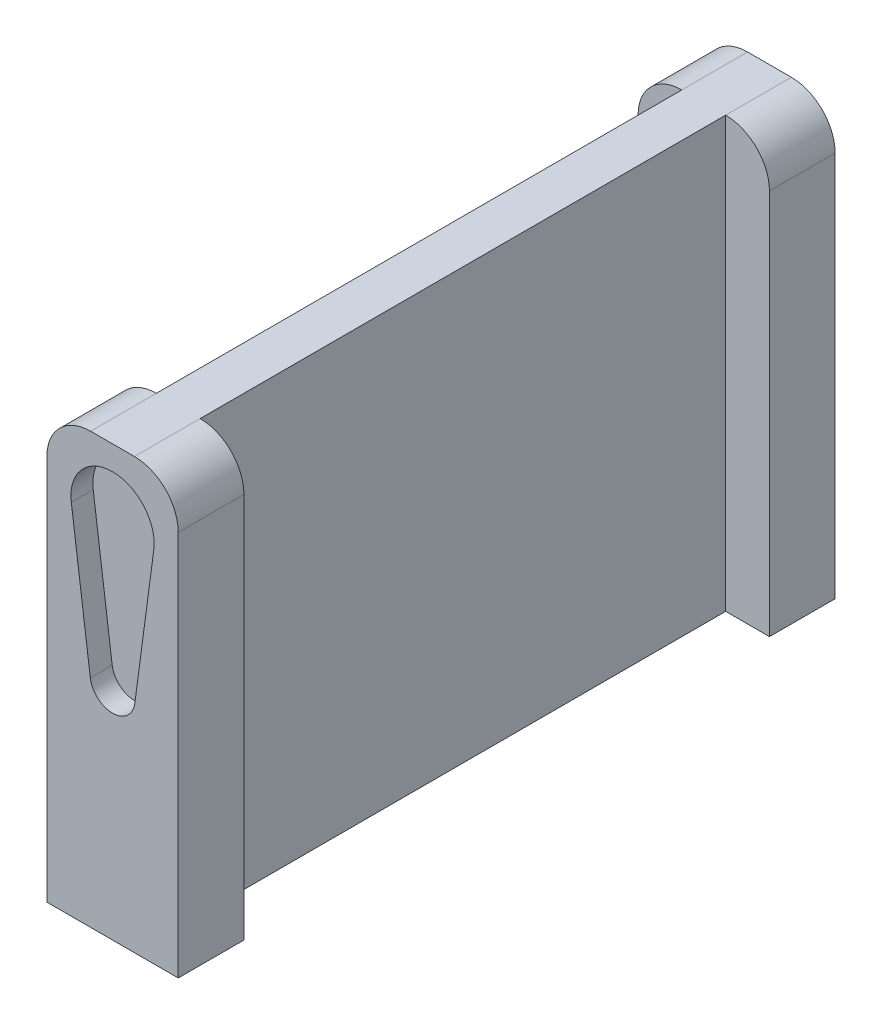
SolidWorks part; units mm, degrees
ref_plane "Front Plane" through (0, 0, 0) normal (0, 0, 1) x (1, 0, 0)
ref_plane "Top Plane" through (0, 0, 0) normal (0, 1, 0) x (1, 0, 0)
ref_plane "Right Plane" through (0, 0, 0) normal (1, 0, 0) x (0, 0, -1)
sketch "Sketch1" plane through (0, 0, 0) normal (0, 0, 1) x (1, 0, 0)
  line L0 (0, 0) -> (0, -13.25) construction
  line L1 (-1.7347, -13.4811) -> (-3.4693, -0.4623) construction
  line L2 (1.7347, -13.4811) -> (3.4693, -0.4623) construction
  circle A0 centre (0, 0) radius 3.5 construction
  circle A1 centre (0, -13.25) radius 1.75 construction
  point P7 (0, -15)
  point P10 (0, 3.5)
  dimension "D1" = 7
  dimension "D3" = 3.5
  dimension "D2" = 18.5
ref_plane "Plane2" through (0, 6, 0) normal (0, 1, 0) x (1, 0, 0)
sketch "Sketch4" plane through (0, 6, 0) normal (0, 1, 0) x (1, 0, 0)
  line L0 (-6, 30) -> (6, 30)
  line L1 (6, 30) -> (6, 24)
  line L2 (6, 24) -> (2, 24)
  line L3 (2, 24) -> (2, -24)
  line L4 (2, -24) -> (6, -24)
  line L5 (6, -24) -> (6, -30)
  line L6 (6, -30) -> (-6, -30)
  line L7 (-6, -30) -> (-6, -24)
  line L8 (-6, -24) -> (-2, -24)
  line L9 (-2, -24) -> (-2, 24)
  line L10 (-2, 24) -> (-6, 24)
  line L11 (-6, 24) -> (-6, 30)
  point P12 (-2, 0)
  point P14 (0, 30)
  dimension "D1" = 6
  dimension "D2" = 60
  dimension "D3" = 6
  dimension "D4" = 4
extrude "Boss-Extrude2" add sketch "Sketch4" against normal blind 39.25
sketch "Sketch5" plane through (0, 0, 30) normal (0, 0, 1) x (1, 0, 0)
  line L0 (3.7667, -0.5019) -> (2.032, -13.5208)
  line L9 (-3.7667, -0.5019) -> (-2.032, -13.5208)
  arc A9 (3.7667, -0.5019) -> (-3.7667, -0.5019) centre (0, 0) ccw
  circle A10 centre (0, 0) radius 3.5 construction
  arc A11 (-2.032, -13.5208) -> (2.032, -13.5208) centre (0, -13.25) ccw
  circle A12 centre (0, -13.25) radius 1.75 construction
  dimension "D1" = 0.3
  dimension "D2" = 0.3
extrude "Cut-Extrude1" cut sketch "Sketch5" against normal blind 2
mirror "Mirror1" about plane through (0, 0, 0) normal (0, 0, 1) of "Cut-Extrude1"
fillet "Fillet1" radius 4 4 edges at (-6, 6, -27) (6, 6, -27) (6, 6, 27) (-6, 6, 27)
